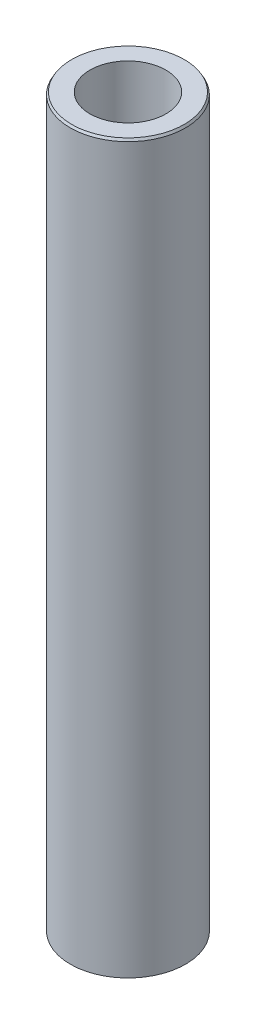
SolidWorks part; units mm, degrees
ref_plane "Front Plane" through (0, 0, 0) normal (0, 0, 1) x (1, 0, 0)
ref_plane "Top Plane" through (0, 0, 0) normal (0, 1, 0) x (1, 0, 0)
ref_plane "Right Plane" through (0, 0, 0) normal (1, 0, 0) x (0, 0, -1)
sketch "Sketch1" plane through (0, 0, 0) normal (0, 1, 0) x (1, 0, 0)
  circle A0 centre (0, 0) radius 47.5
  dimension "SHAFT_OD" = 95
extrude "Boss-Extrude1" add sketch "Sketch1" along normal blind 600
sketch "Sketch2" plane through (0, 0, 0) normal (0, 1, 0) x (1, 0, 0)
  circle A0 centre (0, 0) radius 31.3224
  dimension "BORE_D" = 62.6449
extrude "Cut-Extrude1" cut sketch "Sketch2" along normal through all
chamfer "Chamfer1" distance 1.9312 angle 30 2 edges at (0, 600, 47.5) (0, 0, 47.5) first distance on face at (0, 600, 47.5) first distance on face at (0, 0, 31.3224)
